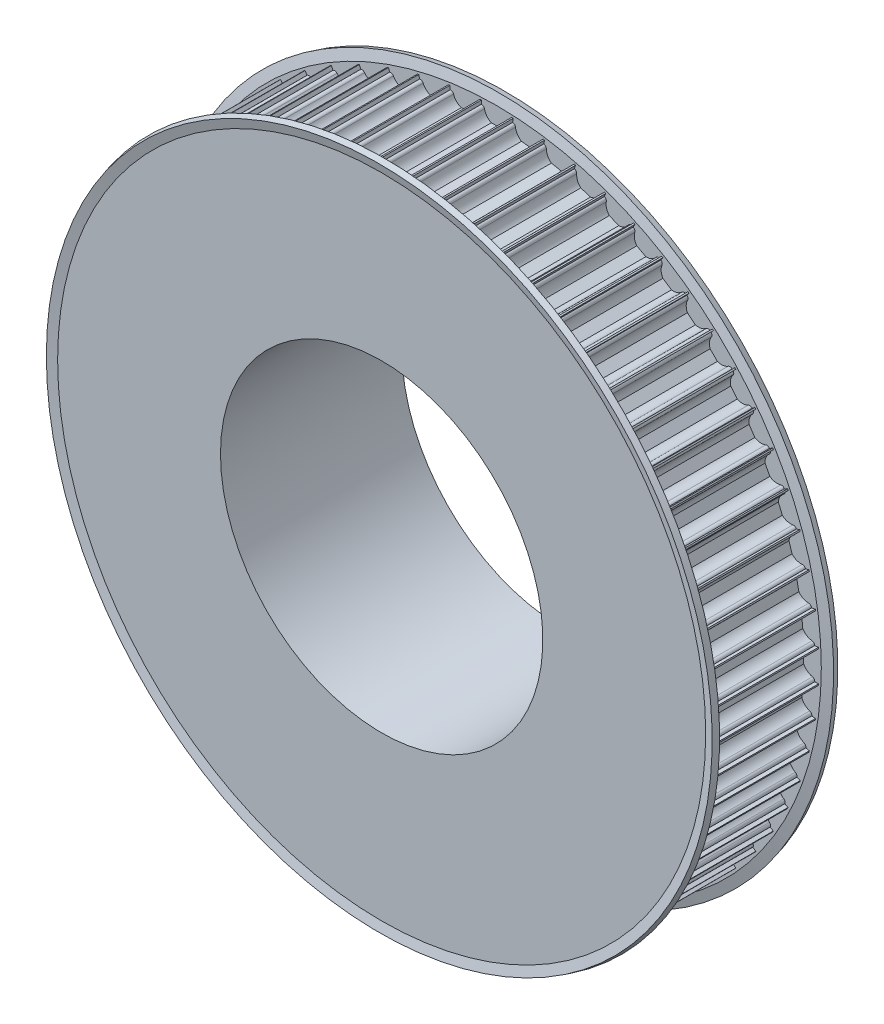
SolidWorks part; units mm, degrees
ref_plane "Front Plane" through (0, 0, 0) normal (0, 0, 1) x (1, 0, 0)
ref_plane "Top Plane" through (0, 0, 0) normal (0, 1, 0) x (1, 0, 0)
ref_plane "Right Plane" through (0, 0, 0) normal (1, 0, 0) x (0, 0, -1)
ref_axis "Axis1" through (0, 0, -88.99) along (0, 0, 1)
sketch "Sketch1" plane through (0, 0, 0) normal (1, 0, 0) x (0, 0, -1)
  line L0 (0, 40) -> (0, 80)
  line L1 (0, 80) -> (30, 80)
  line L2 (30, 80) -> (30, 55.5)
  line L3 (30, 55.5) -> (45, 55.5)
  line L4 (45, 55.5) -> (45, 40)
  line L5 (45, 40) -> (0, 40)
  line L6 (88.99, 0) -> (-88.99, 0) construction
  dimension "D1" = 30
  dimension "D2" = 40
  dimension "D3" = 15
  dimension "D4" = 15.5
  dimension "D5" = 40
revolve "Revolve1" add sketch "Sketch1" angle 360 about axis through (0, 0, -88.99) along (0, 0, 1)
sketch "Sketch2" plane through (0, 0, 0) normal (0, 0, 1) x (1, 0, 0)
  line L0 (3.7071, 79) -> (3.75, 79)
  line L1 (-3.75, 81) -> (3.75, 81)
  line L2 (-3.75, 81) -> (-3.75, 79)
  line L3 (-3.75, 79) -> (-3.7071, 79)
  line L4 (3.75, 81) -> (3.75, 79)
  line L5 (-3.75, 81) -> (3.75, 79) construction
  line L6 (-3.75, 79) -> (3.75, 81) construction
  line L7 (1.2774, 76.25) -> (-1.2774, 76.25)
  arc A1 (-2.972, 78.3987) -> (-1.2774, 76.25) centre (0, 79) ccw
  arc A2 (-2.972, 78.3987) -> (-3.7071, 79) centre (-3.7071, 78.25) ccw
  arc A3 (2.972, 78.3987) -> (3.7071, 79) centre (3.7071, 78.25) cw
  arc A4 (1.2774, 76.25) -> (2.972, 78.3987) centre (0, 79) ccw
  point P3 (0, 80)
  point P15 (3.0322, 79)
  dimension "D3" = 79
  dimension "D5" = 0.75
  dimension "D4" = 0.75
  dimension "D1" = 2
  dimension "D2" = 7.5
  dimension "D6" = 2.75
extrude "Cut-Extrude1" cut sketch "Sketch2" against normal blind 48
pattern_circular "CirPattern1" count 64 over 360 about axis through (0, 0, -88.99) along (0, 0, 1) of "Cut-Extrude1"
sketch "Sketch3" plane through (0, 0, 0) normal (1, 0, 0) x (0, 0, -1)
  line L0 (1.5, 80.6121) -> (0.0511, 80.2238) construction
  line L1 (0, 80.6121) -> (1.5, 80.6121)
  line L2 (0, 80.6121) -> (0, 75.6121)
  line L3 (0, 75.6121) -> (1.5, 75.6121)
  line L4 (1.5, 80.6121) -> (1.5, 75.6121)
  line L5 (1.5, 80.6121) -> (0.8569, 83.0121)
  line L6 (0.0511, 80.2238) -> (-0.592, 82.6238)
  line L7 (0.8569, 83.0121) -> (-0.592, 82.6238)
  line L8 (0, -37.0706) -> (0, -39.578) construction
  line L9 (0, 79.9121) -> (30, 79.9121) construction
  line L10 (15, -40.9775) -> (15, 34.3631) construction
  line L11 (30, -40.9775) -> (0, -40.9775) construction
  line L12 (30, 34.3631) -> (0, 34.3631) construction
  line L13 (28.5, 80.6121) -> (29.9489, 80.2238) construction
  line L14 (29.1431, 83.0121) -> (30.592, 82.6238)
  line L15 (29.9489, 80.2238) -> (30.592, 82.6238)
  line L16 (28.5, 80.6121) -> (29.1431, 83.0121)
  line L17 (28.5, 80.6121) -> (28.5, 75.6121)
  line L18 (30, 75.6121) -> (28.5, 75.6121)
  line L19 (30, 80.6121) -> (30, 75.6121)
  line L20 (30, 80.6121) -> (28.5, 80.6121)
  dimension "D1" = 1.5
  dimension "D2" = 5
  dimension "D3" = 1.5
  dimension "D4" = 165
  dimension "D5" = 2.4
  dimension "D6" = 0.7
revolve "Revolve2" add sketch "Sketch3" angle 360 about axis through (0, 0, -88.99) along (0, 0, 1) region at (0, 81.7161, -0.4493) region at (0, 78.1121, -0.75) region at (0, 81.7161, -29.5507) region at (0, 78.1121, -29.25)
